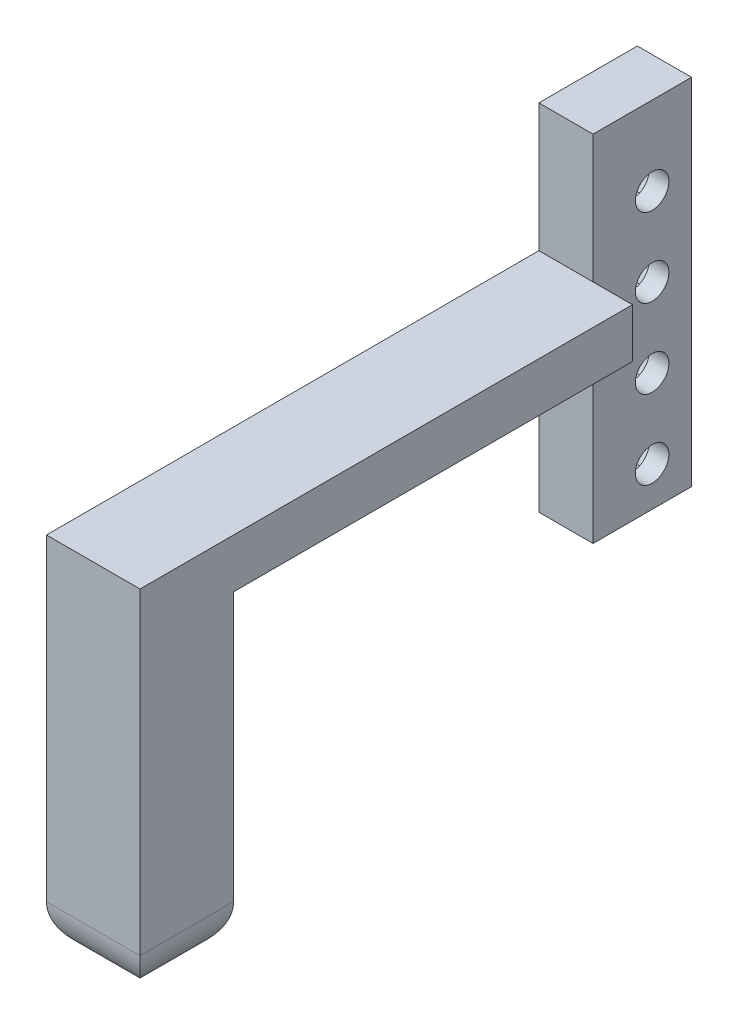
SolidWorks part; units mm, degrees
ref_plane "Plan de face" through (0, 0, 0) normal (0, 0, 1) x (1, 0, 0)
ref_plane "Plan de dessus" through (0, 0, 0) normal (0, 1, 0) x (1, 0, 0)
ref_plane "Plan de droite" through (0, 0, 0) normal (1, 0, 0) x (0, 0, -1)
sketch "Esquisse1" plane through (0, 0, 0) normal (0, 0, 1) x (1, 0, 0)
  line L1 (-2.75, -18) -> (2.75, -18)
  line L2 (-2.75, -18) -> (-2.75, 18)
  line L3 (-2.75, 18) -> (2.75, 18)
  line L4 (2.75, -18) -> (2.75, 18)
  line L5 (-2.75, -18) -> (2.75, 18) construction
  line L6 (-2.75, 18) -> (2.75, -18) construction
  point P1 (0, 0)
  dimension "D1" = 5.5
  dimension "D2" = 36
extrude "Boss.-Extru.1" add sketch "Esquisse1" along normal blind 10
sketch "Esquisse2" plane through (2.75, 0, 0) normal (1, 0, 0) x (0, 0, -1)
  line L0 (-4, 18) -> (-4, -18) construction
  line L1 (-10, 18) -> (0, 18) construction
  line L2 (-10, -18) -> (0, -18) construction
  line L3 (-10, -18) -> (-10, 18) construction
  circle A0 centre (-4, 10) radius 1.7
  circle A1 centre (-4, 2) radius 1.7
  circle A2 centre (-4, -6) radius 1.7
  circle A3 centre (-4, -14) radius 1.7
  dimension "D2" = 8
  dimension "D1" = 6
  dimension "D3" = 4
extrude "Enlèv. mat.-Extru.1" cut sketch "Esquisse2" against normal blind 4
sketch "Esquisse3" plane through (-2.75, 0, 0) normal (1, 0, 0) x (0, 0, -1)
  line L0 (-2.5741, 4.9018) -> (-5.8001, 4.6857)
  line L1 (-2.5741, 12.9018) -> (-5.8001, 12.6857)
  line L2 (-5.8001, 12.6857) -> (-7.2259, 9.784)
  line L3 (-7.2259, 9.784) -> (-5.4259, 7.0982)
  line L4 (-5.4259, 7.0982) -> (-2.1999, 7.3143)
  line L5 (-2.1999, 7.3143) -> (-0.7741, 10.216)
  line L6 (-0.7741, 10.216) -> (-2.5741, 12.9018)
  line L7 (-5.8001, 4.6857) -> (-7.2259, 1.784)
  line L8 (-7.2259, 1.784) -> (-5.4259, -0.9018)
  line L9 (-5.4259, -0.9018) -> (-2.1999, -0.6857)
  line L10 (-2.1999, -0.6857) -> (-0.7741, 2.216)
  line L11 (-0.7741, 2.216) -> (-2.5741, 4.9018)
  line L12 (-2.5741, -3.0982) -> (-5.8001, -3.3143)
  line L13 (-5.8001, -3.3143) -> (-7.2259, -6.216)
  line L14 (-7.2259, -6.216) -> (-5.4259, -8.9018)
  line L15 (-5.4259, -8.9018) -> (-2.1999, -8.6857)
  line L16 (-2.1999, -8.6857) -> (-0.7741, -5.784)
  line L17 (-0.7741, -5.784) -> (-2.5741, -3.0982)
  line L18 (-2.5741, -11.0982) -> (-5.8001, -11.3143)
  line L19 (-5.8001, -11.3143) -> (-7.2259, -14.216)
  line L20 (-7.2259, -14.216) -> (-5.4259, -16.9018)
  line L21 (-5.4259, -16.9018) -> (-2.1999, -16.6857)
  line L22 (-2.1999, -16.6857) -> (-0.7741, -13.784)
  line L23 (-0.7741, -13.784) -> (-2.5741, -11.0982)
  circle A0 centre (-4, 10) radius 2.8 construction
  dimension "D1" = 4
extrude "Enlèv. mat.-Extru.2" cut sketch "Esquisse3" along normal blind 3.5 draft 5
sketch "Esquisse4" plane through (0, 0, 10) normal (0, 0, 1) x (1, 0, 0)
  line L0 (-2.75, 18) -> (-2.75, -18) construction
  line L1 (-2.75, 5) -> (6.75, 5)
  line L2 (-2.75, 5) -> (-2.75, 0)
  line L3 (-2.75, 0) -> (6.75, 0)
  line L4 (6.75, 5) -> (6.75, 0)
  line L6 (2.75, 18) -> (-2.75, 18) construction
  dimension "D1" = 9.5
  dimension "D2" = 5
  dimension "D3" = 18
extrude "Boss.-Extru.2" add sketch "Esquisse4" along normal blind 50
sketch "Esquisse5" plane through (0, 0, 0) normal (0, -1, 0) x (1, 0, 0)
  line L0 (6.75, 60) -> (6.75, 10) construction
  line L1 (-2.75, 60) -> (6.75, 60)
  line L2 (-2.75, 60) -> (-2.75, 50.5)
  line L3 (-2.75, 50.5) -> (6.75, 50.5)
  line L4 (6.75, 60) -> (6.75, 50.5)
  dimension "D1" = 9.5
extrude "Boss.-Extru.3" add sketch "Esquisse5" along normal blind 32
fillet "Congé1" radius 4.75 4 edges at (2, -32, 50.5) (6.75, -32, 55.25) (2, -32, 60) (-2.75, -32, 55.25)
